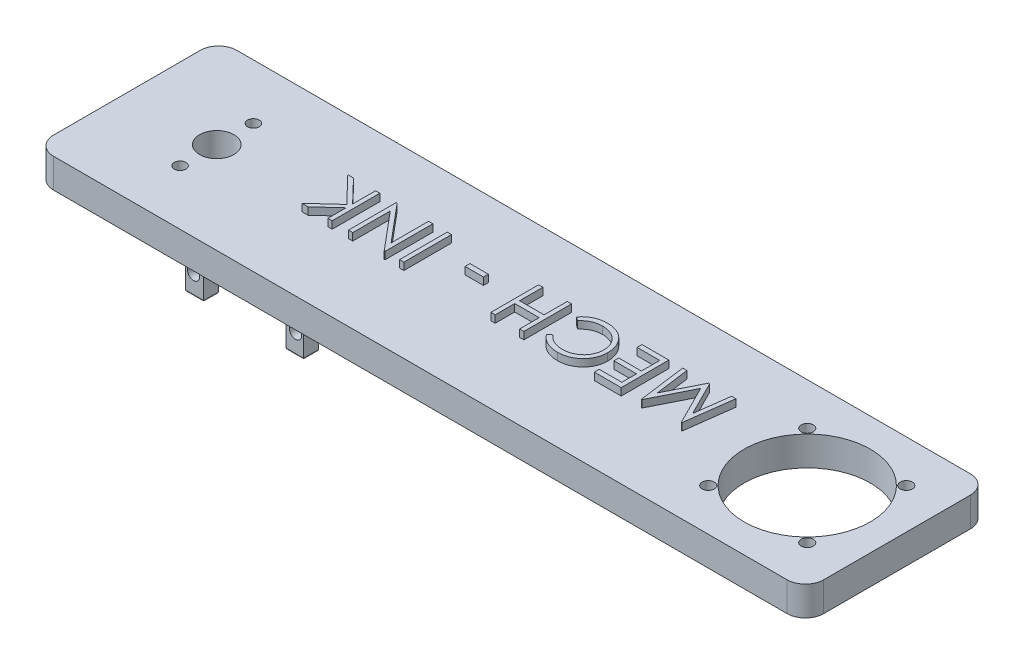
SolidWorks part; units mm, degrees
ref_plane "Front Plane" through (0, 0, 0) normal (0, 0, 1) x (1, 0, 0)
ref_plane "Top Plane" through (0, 0, 0) normal (0, 1, 0) x (1, 0, 0)
ref_plane "Right Plane" through (0, 0, 0) normal (1, 0, 0) x (0, 0, -1)
sketch "Croquis1" plane through (0, 0, 0) normal (0, 1, 0) x (1, 0, 0)
  line L1 (-105, 25) -> (105, 25)
  line L2 (-105, 25) -> (-105, -25)
  line L3 (-105, -25) -> (105, -25)
  line L4 (105, 25) -> (105, -25)
  line L5 (-105, 25) -> (105, -25) construction
  line L6 (-105, -25) -> (105, 25) construction
  line L7 (-97.8979, 19.0049) -> (-63.1021, 19.0049) construction
  line L8 (-97.8979, 19.0049) -> (-97.8979, -19.0049) construction
  line L9 (-97.8979, -19.0049) -> (-63.1021, -19.0049) construction
  line L10 (-63.1021, 19.0049) -> (-63.1021, -19.0049) construction
  line L11 (-97.8979, 19.0049) -> (-63.1021, -19.0049) construction
  line L12 (-97.8979, -19.0049) -> (-63.1021, 19.0049) construction
  circle A0 centre (-80.5, 0) radius 4.7
  circle A1 centre (80.5, 0) radius 17.2
  circle A10 centre (67, 13.5) radius 1.65
  circle A11 centre (94, 13.5) radius 1.65
  circle A12 centre (94, -13.5) radius 1.65
  circle A13 centre (67, -13.5) radius 1.65
  circle A14 centre (-80.5, 10) radius 1.6
  circle A15 centre (-80.5, -10) radius 1.6
  point P0 (0, 0)
  dimension "D4" = 9.4
  dimension "D7" = 34.4
  dimension "D1" = 210
  dimension "D2" = 50
  dimension "D3" = 161
  dimension "D5" = 24.5
  dimension "D8" = 5.9951
  dimension "D9" = 7.1021
  dimension "D12" = 38.0099
  dimension "D13" = 34.7958
extrude "Saliente-Extruir1" add sketch "Croquis1" along normal blind 8
extrude "Saliente-Extruir2" add sketch "Croquis1<3>" along normal blind 8
sketch "Croquis1<3>" plane through (0, 0, 0) normal (0, 1, 0) x (1, 0, 0) same geometry as "Croquis1"
extrude "Saliente-Extruir3" add sketch "Croquis1<4>" along normal blind 6 contours L4 L1 L2 L3 A1 A0 region at (-7.4797, 0, 0)
sketch "Croquis1<4>" plane through (0, 0, 0) normal (0, 1, 0) x (1, 0, 0) same geometry as "Croquis1"
sketch "Croquis2" plane through (0, 8, 0) normal (0, 1, 0) x (1, 0, 0)
  line L0 (-57.664, 8.7593) -> (57.664, 8.7593) construction
  text T0 "MECH - INK" font "Century Gothic" height 13
  point P4 (0, 0)
extrude "Saliente-Extruir4" add sketch "Croquis2" along normal blind 2
sketch "Croquis3" plane through (0, 0, 0) normal (0, -1, 0) x (1, 0, 0)
  line L0 (-105, 25) -> (105, 25) construction
  line L1 (-67.0567, 17) -> (-67.0567, 13)
  line L2 (-72.02, 17) -> (-67.0567, 17)
  line L3 (-72.02, 17) -> (-72.02, 13)
  line L4 (-72.02, 13) -> (-67.0567, 13)
  line L5 (-39.8, 17) -> (-39.8, 13)
  line L10 (-44.5567, 17) -> (-44.5567, 13)
  line L11 (-44.5567, 17) -> (-39.8, 17)
  line L12 (-44.5567, 13) -> (-39.8, 13)
  line L13 (-73.6448, 11.4) -> (-36.9929, 11.4) construction
  line L14 (-44.5567, 5.8) -> (-39.8, 5.8)
  line L15 (-44.5567, 5.8) -> (-44.5567, 9.8)
  line L16 (-44.5567, 9.8) -> (-39.8, 9.8)
  line L17 (-39.8, 5.8) -> (-39.8, 9.8)
  line L18 (-72.02, 5.8) -> (-72.02, 9.8)
  line L19 (-72.02, 9.8) -> (-67.0567, 9.8)
  line L20 (-67.0567, 5.8) -> (-67.0567, 9.8)
  line L21 (-72.02, 5.8) -> (-67.0567, 5.8)
  dimension "D1" = 32.22
  dimension "D2" = 4
  dimension "D3" = 22.5
  dimension "D4" = 39.8
  dimension "D5" = 12
  dimension "D6" = 1.6
extrude "Saliente-Extruir6" add sketch "Croquis3" along normal blind 14 contours L2 L1 L4 L3 | L5 L12 L10 L11 | L18 L19 L20 L21 | L14 L17 L16 L15
fillet "Redondeo1" radius 1.5 12 edges at (-42.1783, 0, 17) (-39.8, 0, 15) (-42.1783, 0, 13) (-69.5383, 0, 17) (-69.5383, 0, 13) (-72.02, 0, 15) (-42.1783, 0, 9.8) (-39.8, 0, 7.8) (-42.1783, 0, 5.8) (-69.5383, 0, 5.8) (-72.02, 0, 7.8) (-69.5383, 0, 9.8)
fillet "Redondeo2" radius 3 4 edges at (-44.5567, 0, 15) (-67.0567, 0, 15) (-44.5567, 0, 7.8) (-67.0567, 0, 7.8)
sketch "Croquis4" plane through (0, 0, 17) normal (0, 0, 1) x (1, 0, 0)
  circle A0 centre (-42.0238, -8.6) radius 1.65
  circle A1 centre (-69.8238, -8.6) radius 1.65
  dimension "D1" = 3.3
  dimension "D2" = 3.3
extrude "Cortar-Extruir1" cut sketch "Croquis4" against normal blind 14
fillet "Redondeo3" radius 0.5 16 edges at (-69.5383, -14, 17) (-67.0567, -14, 15) (-69.5383, -14, 13) (-72.02, -14, 15) (-72.02, -14, 7.8) (-69.5383, -14, 9.8) (-67.0567, -14, 7.8) (-69.5383, -14, 5.8) (-39.8, -14, 15) (-42.1783, -14, 13) (-44.5567, -14, 15) (-42.1783, -14, 17) (-42.1783, -14, 9.8) (-39.8, -14, 7.8) (-42.1783, -14, 5.8) (-44.5567, -14, 7.8)
fillet "Redondeo4" radius 5 4 edges at (105, 4, -25) (105, 4, 25) (-105, 4, 25) (-105, 4, -25)
